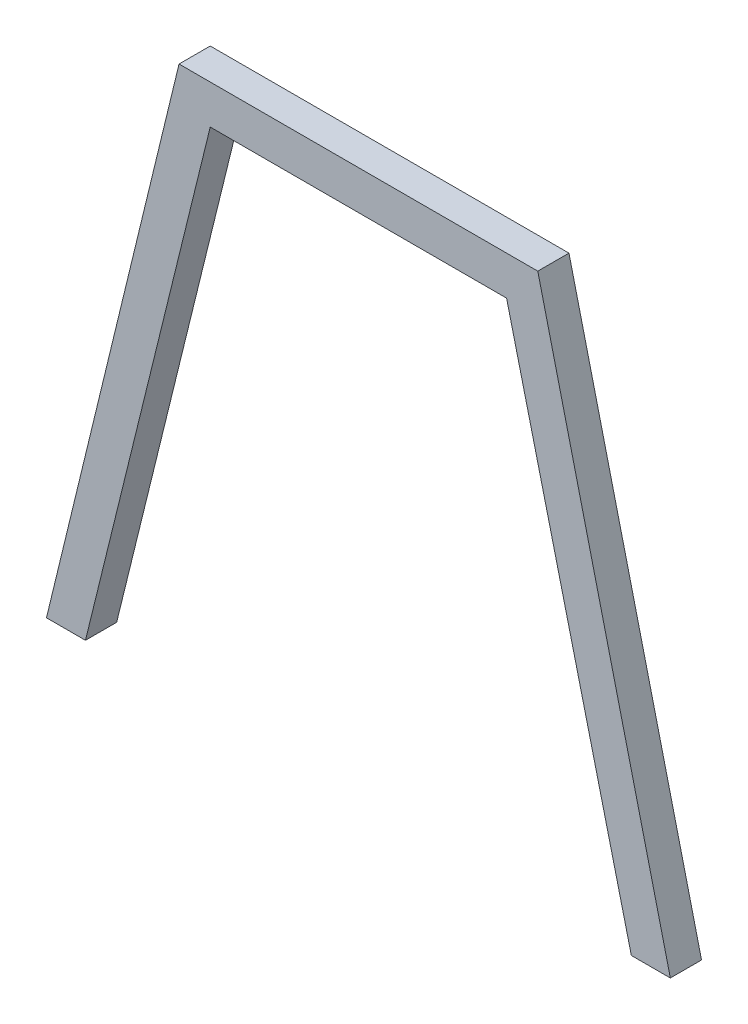
SolidWorks part; units mm, degrees
material "AISI 304"
ref_plane "Front Plane" through (0, 0, 0) normal (0, 0, 1) x (1, 0, 0)
ref_plane "Top Plane" through (0, 0, 0) normal (0, 1, 0) x (1, 0, 0)
ref_plane "Right Plane" through (0, 0, 0) normal (1, 0, 0) x (0, 0, -1)
sketch "A_Frame_Profile" plane through (0, 0, 0) normal (0, 0, 1) x (1, 0, 0)
  line L0 (-200, 0) -> (-115, 350)
  line L1 (-115, 350) -> (115, 350)
  line L2 (115, 350) -> (200, 0)
  line L3 (200, 0) -> (175, 0)
  line L4 (175, 0) -> (95, 325)
  line L5 (95, 325) -> (-95, 325)
  line L6 (-95, 325) -> (-175, 0)
  line L7 (-175, 0) -> (-200, 0)
  dimension "D1" = 95
  dimension "D3" = 175
  dimension "D4" = 200
  dimension "D5" = 95
  dimension "D6" = 325
  dimension "D7" = 350
  dimension "Half_Top_Width" = 115
extrude "A_Frame_Blank" add sketch "A_Frame_Profile" along normal mid plane 20
shell "Hollow_Wall_2mm" thickness 2
